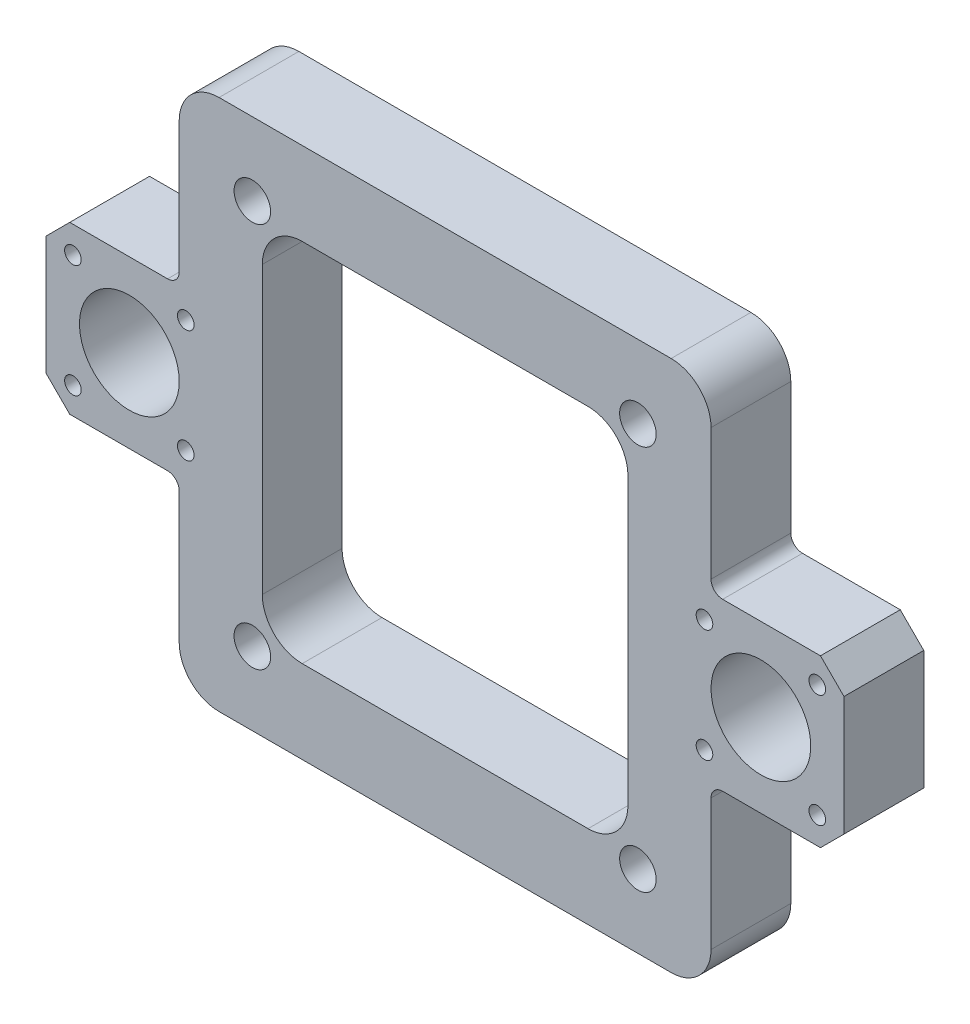
SolidWorks part; units mm, degrees
ref_plane "Front Plane" through (0, 0, 0) normal (0, 0, 1) x (1, 0, 0)
ref_plane "Top Plane" through (0, 0, 0) normal (0, 1, 0) x (1, 0, 0)
ref_plane "Right Plane" through (0, 0, 0) normal (1, 0, 0) x (0, 0, -1)
sketch "Sketch1" plane through (0, 0, 0) normal (0, 0, 1) x (1, 0, 0)
  line L0 (-47.5, 0) -> (47.5, 0) construction
  line L1 (0, 0) -> (0, 17.3262) construction
  line L2 (-56.4645, 12.5) -> (-41.75, 12.5)
  line L3 (-40, 14.25) -> (-40, 34)
  line L12 (-56.4645, 12.5) -> (-60, 8.9645)
  line L13 (-60, 8.9645) -> (-60, -8.9645)
  line L14 (34, 40) -> (-34, 40)
  line L15 (60, 8.9645) -> (60, -8.9645)
  line L16 (56.4645, 12.5) -> (60, 8.9645)
  line L17 (56.4645, 12.5) -> (41.75, 12.5)
  line L18 (40, 14.25) -> (40, 34)
  line L19 (-56.4645, -12.5) -> (-60, -8.9645)
  line L20 (-56.4645, -12.5) -> (-41.75, -12.5)
  line L21 (-40, -14.25) -> (-40, -34)
  line L22 (34, -40) -> (-34, -40)
  line L23 (40, -14.25) -> (40, -34)
  line L24 (56.4645, -12.5) -> (41.75, -12.5)
  line L25 (56.4645, -12.5) -> (60, -8.9645)
  line L26 (-55.9853, 8.4853) -> (-39.0147, -8.4853) construction
  line L27 (-55.9853, -8.4853) -> (-39.0147, 8.4853) construction
  circle A0 centre (-47.5, 0) radius 7.5
  arc A12 (-41.75, 12.5) -> (-40, 14.25) centre (-41.75, 14.25) ccw
  arc A13 (-40, 34) -> (-34, 40) centre (-34, 34) cw
  arc A14 (41.75, 12.5) -> (40, 14.25) centre (41.75, 14.25) cw
  arc A15 (40, 34) -> (34, 40) centre (34, 34) ccw
  arc A16 (-41.75, -12.5) -> (-40, -14.25) centre (-41.75, -14.25) cw
  arc A17 (-40, -34) -> (-34, -40) centre (-34, -34) ccw
  arc A18 (40, -34) -> (34, -40) centre (34, -34) cw
  arc A19 (41.75, -12.5) -> (40, -14.25) centre (41.75, -14.25) ccw
  circle A20 centre (47.5, 0) radius 7.5
  circle A21 centre (-55.9853, 8.4853) radius 1.75 construction
  circle A22 centre (-39.0147, -8.4853) radius 1.75 construction
  circle A23 centre (-39.0147, 8.4853) radius 1.75 construction
  circle A24 centre (-55.9853, -8.4853) radius 1.75 construction
  circle A25 centre (39.0147, -8.4853) radius 1.75 construction
  circle A26 centre (55.9853, -8.4853) radius 1.75 construction
  circle A27 centre (55.9853, 8.4853) radius 1.75 construction
  circle A28 centre (39.0147, 8.4853) radius 1.75 construction
  circle A29 centre (-29, 29) radius 2.75
  circle A33 centre (29, 29) radius 2.75
  circle A34 centre (29, -29) radius 2.75
  circle A35 centre (-29, -29) radius 2.75
  point P28 (0, 40)
  point P29 (-60, 0)
  point P44 (60, 0)
  dimension "D2" = 15
  dimension "D3" = 25
  dimension "D6" = 1.75
  dimension "D11" = 3.5
  dimension "D13" = 6
  dimension "D15" = 5.5
  dimension "D1" = 95
  dimension "D4" = 120
  dimension "D5" = 40
  dimension "D7" = 135
  dimension "D8" = 80
  dimension "D9" = 5
  dimension "D10" = 24
  dimension "D12" = 135
  dimension "D14" = 58
  dimension "D16" = 58
extrude "Boss-Extrude1" add sketch "Sketch1" along normal blind 12
sketch "Sketch4" [suppressed] plane through (0, 0, 12) normal (0, 0, 1) x (1, 0, 0)
  circle A0 centre (55.9853, 8.4853) radius 1.75 construction
  circle A1 centre (55.9853, -8.4853) radius 1.75 construction
  circle A2 centre (39.0147, -8.4853) radius 1.75 construction
  circle A3 centre (39.0147, 8.4853) radius 1.75 construction
  circle A4 centre (-39.0147, 8.4853) radius 1.75 construction
  circle A5 centre (-39.0147, -8.4853) radius 1.75 construction
  circle A6 centre (-55.9853, -8.4853) radius 1.75 construction
  circle A7 centre (-55.9853, 8.4853) radius 1.75 construction
  circle A8 centre (55.9853, 8.4853) radius 1.75
  circle A9 centre (55.9853, -8.4853) radius 1.75
  circle A10 centre (39.0147, -8.4853) radius 1.75
  circle A11 centre (39.0147, 8.4853) radius 1.75
  circle A12 centre (-39.0147, 8.4853) radius 1.75
  circle A13 centre (-39.0147, -8.4853) radius 1.75
  circle A14 centre (-55.9853, -8.4853) radius 1.75
  circle A15 centre (-55.9853, 8.4853) radius 1.75
extrude "Cut-Extrude3" [suppressed] cut sketch "Sketch4" against normal through all both and the other way through all
sketch "Sketch2" plane through (0, 0, 12) normal (0, 0, 1) x (1, 0, 0)
  line L0 (-21.5, 21.5) -> (21.5, -21.5) construction
  line L1 (-21.5, 27.5) -> (21.5, 27.5)
  line L2 (-27.5, 21.5) -> (-27.5, -21.5)
  line L3 (-21.5, -27.5) -> (21.5, -27.5)
  line L4 (27.5, 21.5) -> (27.5, -21.5)
  arc A0 (-27.5, -21.5) -> (-21.5, -27.5) centre (-21.5, -21.5) ccw
  arc A1 (21.5, -27.5) -> (27.5, -21.5) centre (21.5, -21.5) ccw
  arc A2 (27.5, 21.5) -> (21.5, 27.5) centre (21.5, 21.5) ccw
  arc A3 (-21.5, 27.5) -> (-27.5, 21.5) centre (-21.5, 21.5) ccw
  dimension "D1" = 6
  dimension "D2" = 55
extrude "Cut-Extrude1" cut sketch "Sketch2" against normal through all both and the other way through all
sketch "Sketch3" plane through (0, 0, 12) normal (0, 0, 1) x (1, 0, 0)
  line L0 (-56.4645, 12.5) -> (-60, 8.9645) construction
  line L1 (-55.1485, 5.3623) -> (-52.8623, 7.6485)
  line L2 (-52.8623, 7.6485) -> (-53.6991, 10.7715)
  line L3 (-53.6991, 10.7715) -> (-56.8221, 11.6083)
  line L4 (-56.8221, 11.6083) -> (-59.1083, 9.3221)
  line L5 (-59.1083, 9.3221) -> (-58.2715, 6.1991)
  line L6 (-58.2715, 6.1991) -> (-55.1485, 5.3623)
  line L7 (-42.1377, 7.6485) -> (-39.8515, 5.3623)
  line L8 (-39.8515, 5.3623) -> (-36.7285, 6.1991)
  line L9 (-36.7285, 6.1991) -> (-35.8917, 9.3221)
  line L10 (-35.8917, 9.3221) -> (-38.1779, 11.6083)
  line L11 (-38.1779, 11.6083) -> (-41.3009, 10.7715)
  line L12 (-41.3009, 10.7715) -> (-42.1377, 7.6485)
  line L13 (-39.8515, -5.3623) -> (-42.1377, -7.6485)
  line L14 (-42.1377, -7.6485) -> (-41.3009, -10.7715)
  line L15 (-41.3009, -10.7715) -> (-38.1779, -11.6083)
  line L16 (-38.1779, -11.6083) -> (-35.8917, -9.3221)
  line L17 (-35.8917, -9.3221) -> (-36.7285, -6.1991)
  line L18 (-36.7285, -6.1991) -> (-39.8515, -5.3623)
  line L19 (-52.8623, -7.6485) -> (-55.1485, -5.3623)
  line L20 (-55.1485, -5.3623) -> (-58.2715, -6.1991)
  line L21 (-58.2715, -6.1991) -> (-59.1083, -9.3221)
  line L22 (-59.1083, -9.3221) -> (-56.8221, -11.6083)
  line L23 (-56.8221, -11.6083) -> (-53.6991, -10.7715)
  line L24 (-53.6991, -10.7715) -> (-52.8623, -7.6485)
  circle A0 centre (-55.9853, 8.4853) radius 2.8 construction
  circle A2 centre (-47.5, 0) radius 7.5 construction
  circle A3 centre (-47.5, 0) radius 7.5 construction
  circle A4 centre (-39.0147, 8.4853) radius 2.8 construction
  circle A5 centre (-39.0147, -8.4853) radius 2.8 construction
  circle A6 centre (-55.9853, -8.4853) radius 2.8 construction
  point P42 (-47.5, 0)
  dimension "D1" = 5.6
  dimension "D2" = 4
extrude "Cut-Extrude2" [suppressed] cut sketch "Sketch3" against normal blind 2.5
mirror "Mirror1" [suppressed] about plane through (0, 0, 0) normal (1, 0, 0)
sketch "Sketch5" plane through (0, 0, 0) normal (0, 0, -1) x (-1, 0, 0)
  point P0 (55.9853, -8.4853)
  point P3 (55.9853, 8.4853)
  point P6 (39.0147, 8.4853)
  point P9 (39.0147, -8.4853)
  point P12 (-39.0147, -8.4853)
  point P15 (-39.0147, 8.4853)
  point P18 (-55.9853, 8.4853)
  point P21 (-55.9853, -8.4853)
hole_wizard "Tap Drill for M3x0.5 Tap1" positions "Sketch5" profile "Sketch6" hole size "M3x0.5" standard "ANSI Metric" end condition through all
sketch "Sketch6" plane through (-55.9853, -8.4853, 0) normal (1, 0, 0) x (0, 1, 0)
  line L0 (0, 0) -> (0, 12)
  line L1 (0, 12) -> (1.25, 12)
  line L2 (1.25, 12) -> (1.25, 0)
  line L5 (1.25, 0) -> (0, 0)
  line L11 (0, -6.35) -> (0, 107.95) construction
  dimension "Thru Hole Dia." = 2.5
  dimension "Thru Hole Depth" = 12
